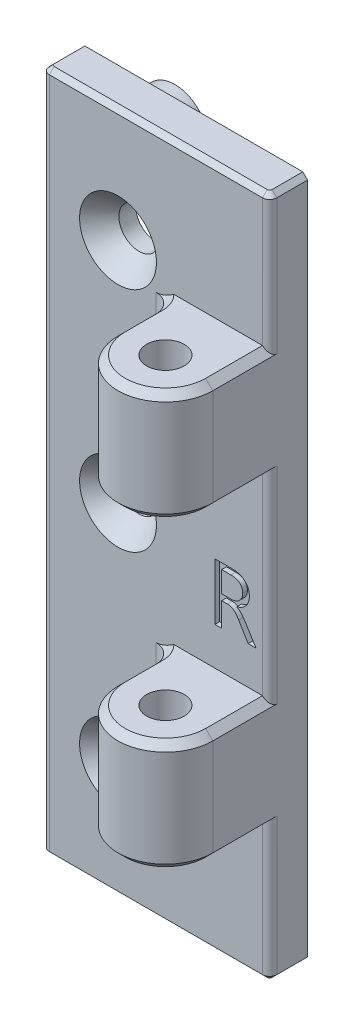
SolidWorks part; units mm, degrees
material "ASA"
ref_plane "Front Plane" through (0, 0, 0) normal (0, 0, 1) x (1, 0, 0)
ref_plane "Top Plane" through (0, 0, 0) normal (0, 1, 0) x (1, 0, 0)
ref_plane "Right Plane" through (0, 0, 0) normal (1, 0, 0) x (0, 0, -1)
sketch "Sketch1" plane through (0, 0, 0) normal (0, 0, 1) x (1, 0, 0)
  line L1 (0, 114.3) -> (38.1, 114.3)
  line L2 (0, 114.3) -> (0, 0)
  line L3 (0, 0) -> (38.1, 0)
  line L4 (38.1, 114.3) -> (38.1, 0)
  dimension "D1" = 38.1
  dimension "D2" = 114.3
extrude "Boss-Extrude1" add sketch "Sketch1" along normal blind 6.35
sketch "Sketch2" plane through (0, 0, 0) normal (0, 0, -1) x (-1, 0, 0)
  line L0 (-38.1, 114.3) -> (0, 114.3) construction
  line L1 (0, 114.3) -> (0, 0) construction
  circle A0 centre (-12.7, 107.5182) radius 6.0706 construction
  circle A1 centre (-12.7, 107.5182) radius 5.5626
  dimension "D4" = 12.1412
  dimension "D1" = 6.7818
  dimension "D2" = 12.7
  dimension "D3" = 0.508
extrude "Boss-Extrude2" add sketch "Sketch2" along normal blind 3.175
fillet "Fillet1" radius 0.762 1 edges at (18.2626, 107.5182, 0)
hole_wizard "CSK for 1/4 Flat Head Machine Screw1" positions "Sketch3" profile "Sketch4" countersink size "1/4" standard "ANSI Inch" end condition through all
sketch "Sketch3" plane through (0, 0, 6.35) normal (0, 0, 1) x (1, 0, 0)
  line L0 (38.1, 114.3) -> (0, 114.3) construction
  line L2 (0, 114.3) -> (0, 0) construction
  point P0 (12.7, 95.25)
  dimension "D1" = 19.05
  dimension "D2" = 12.7
sketch "Sketch4" plane through (12.7, 95.25, 6.35) normal (1, 0, 0) x (0, -1, 0)
  line L0 (0, 0) -> (0, 9.525)
  line L1 (0, 9.525) -> (3.3782, 9.525)
  line L2 (3.3782, 9.525) -> (3.3782, 3.5209)
  line L3 (3.3782, 3.5209) -> (6.4389, 0)
  line L5 (6.4389, 0) -> (0, 0)
  line L6 (-3.3782, 3.5209) -> (-6.4389, 0) construction
  line L11 (0, -6.35) -> (0, 107.95) construction
  dimension "Thru Hole Dia." = 6.7564
  dimension "Thru Hole Depth" = 9.525
  dimension "Near C'Sink Dia." = 12.8778
  dimension "Near C'Sink Angle" = 82
pattern_linear "LPattern1" count 3 spacing 38.1 along (0, -1, 0) of "Boss-Extrude2", "Fillet1", "CSK for 1/4 Flat Head Machine Screw1"
sketch "Sketch5" plane through (0, 114.3, 0) normal (0, 1, 0) x (1, 0, 0)
  line L0 (38.1, -15.875) -> (38.1, 0)
  line L1 (38.1, 0) -> (22.225, 0)
  line L2 (22.225, 0) -> (22.225, -15.875)
  line L3 (38.1, 0) -> (0, 0) construction
  line L4 (38.1, -6.35) -> (38.1, 0) construction
  line L5 (38.1, -6.35) -> (0, -6.35) construction
  arc A0 (22.225, -15.875) -> (38.1, -15.875) centre (30.1625, -15.875) ccw
  dimension "D2" = 7.9375
  dimension "D1" = 9.525
extrude "Boss-Extrude3" add sketch "Sketch5" against normal up to surface (114.3 mm away) up to face at (19.05, 0, 3.175)
sketch "Sketch6" plane through (0, 114.3, 0) normal (0, 1, 0) x (1, 0, 0)
  circle A0 centre (30.1625, -15.875) radius 2.9464
  arc A1 (22.225, -15.875) -> (38.1, -15.875) centre (30.1625, -15.875) ccw construction
  dimension "D1" = 5.8928
extrude "Cut-Extrude1" cut sketch "Sketch6" against normal offset from surface (107.95 mm away) 6.35 up to face at (20.1083, 0, 8.7313)
other "Move Face1" flip direction yes face at (30.1625, 6.35, 18.8214) offset 0.2 parameters "D1"=0.2
sketch "Sketch7" plane through (0, 0, 6.35) normal (0, 0, 1) x (1, 0, 0)
  line L0 (30.1625, 34.6388) -> (30.1625, 84.825) construction
  line L1 (27.0161, 114.3) -> (27.0161, 6.35) construction
  line L2 (33.3089, 6.35) -> (33.3089, 114.3) construction
  line L3 (33.3089, 114.3) -> (27.0161, 114.3) construction
  line L12 (38.1, 0) -> (38.1, 114.3) construction
  line L13 (38.1, 114.3) -> (22.225, 114.3)
  line L14 (38.1, 114.3) -> (38.1, 92.075)
  line L15 (38.1, 92.075) -> (22.225, 92.075)
  line L16 (22.225, 114.3) -> (22.225, 92.075)
  line L17 (38.1, 73.025) -> (22.225, 73.025)
  line L18 (38.1, 73.025) -> (38.1, 41.275)
  line L19 (38.1, 41.275) -> (22.225, 41.275)
  line L20 (22.225, 73.025) -> (22.225, 41.275)
  line L21 (22.225, 0) -> (38.1, 0)
  line L22 (22.225, 0) -> (22.225, 22.225)
  line L23 (22.225, 22.225) -> (38.1, 22.225)
  line L24 (38.1, 0) -> (38.1, 22.225)
  line L25 (38.1, 92.075) -> (38.1, 73.025) construction
  line L26 (38.1, 41.275) -> (38.1, 22.225) construction
  line L28 (0, 0) -> (38.1, 0) construction
  dimension "D1" = 31.75
  dimension "D2" = 22.225
  dimension "D3" = 19.05
extrude "Cut-Extrude2" cut sketch "Sketch7" along normal through all
other "Move Face2" flip direction yes face at (30.1625, 22.225, 13.0969) face at (30.1625, 73.025, 13.0969) offset 0.4 parameters "D1"=0.4
fillet "Fillet2" radius 3.2 2 edges at (22.225, 31.95, 6.35) (22.225, 82.75, 6.35)
fillet "Fillet3" radius 1.2 4 edges at (38.1, 11.3125, 6.35) (38.1, 57.35, 6.35) (38.1, 103.1875, 6.35) (0, 57.15, 6.35)
chamfer "Chamfer1" distance 0.8 angle 45 10 edges at (0, 0, 2.575) (38.1, 0, 2.575) (0.3515, 0, 5.9985) (37.7485, 0, 5.9985) (19.05, 0, 6.35) (38.1, 114.3, 2.575) (0, 114.3, 2.575) (37.7485, 114.3, 5.9985) (0.3515, 114.3, 5.9985) (19.05, 114.3, 6.35)
chamfer "Chamfer2" distance 1.2 angle 45 16 edges at (21.2877, 92.075, 7.2873) (38.1, 92.075, 10.5125) (22.225, 92.075, 12.7125) (30.1625, 92.075, 23.8125) (21.2877, 73.425, 7.2873) (22.225, 73.425, 12.7125) (38.1, 73.425, 10.5125) (30.1625, 73.425, 23.8125) (21.2877, 41.275, 7.2873) (38.1, 41.275, 10.5125) (22.225, 41.275, 12.7125) (30.1625, 41.275, 23.8125) (21.2877, 22.625, 7.2873) (22.225, 22.625, 12.7125) (38.1, 22.625, 10.5125) (30.1625, 22.625, 23.8125)
mirror "Mirror1" about plane through (0, 0, 0) normal (1, 0, 0) of bodies 109
sketch "Sketch8" plane through (0, 0, 6.35) normal (0, 0, 1) x (1, 0, 0)
  line L0 (25.4, 47.625) -> (38.1, 47.625) construction
  line L1 (38.1, 113.5) -> (38.1, 90.875) construction
  line L2 (22.0449, 41.275) -> (36.9, 41.275) construction
  line L3 (-38.1, 47.625) -> (-25.4, 47.625) construction
  line L4 (-38.1, 113.5) -> (-38.1, 90.875) construction
  text T0 "R" font "Segoe UI" height 9.525
  text T1 "L" font "Segoe UI" height 9.525
  dimension "D1" = 12.7
  dimension "D2" = 6.35
extrude "Cut-Extrude3" cut sketch "Sketch8" against normal blind 0.8
delete or keep bodies "Body-Delete/Keep 1" type keep bodies bodies 110
delete or keep bodies "Body-Delete/Keep 2" [suppressed] type keep bodies bodies 112
equation "\"D1@Move Face1\"= 0.2mm"
equation "\"D1@Move Face2\"= 0.4mm"
equation "\"D1@Fillet2\"=3.2mm"
equation "\"D1@Fillet3\"=1.2mm"
equation "\"D1@Chamfer1\"=0.8mm"
equation "\"D1@Chamfer2\"=1.2mm"
equation "\"D1@Cut-Extrude3\"=0.8mm"
